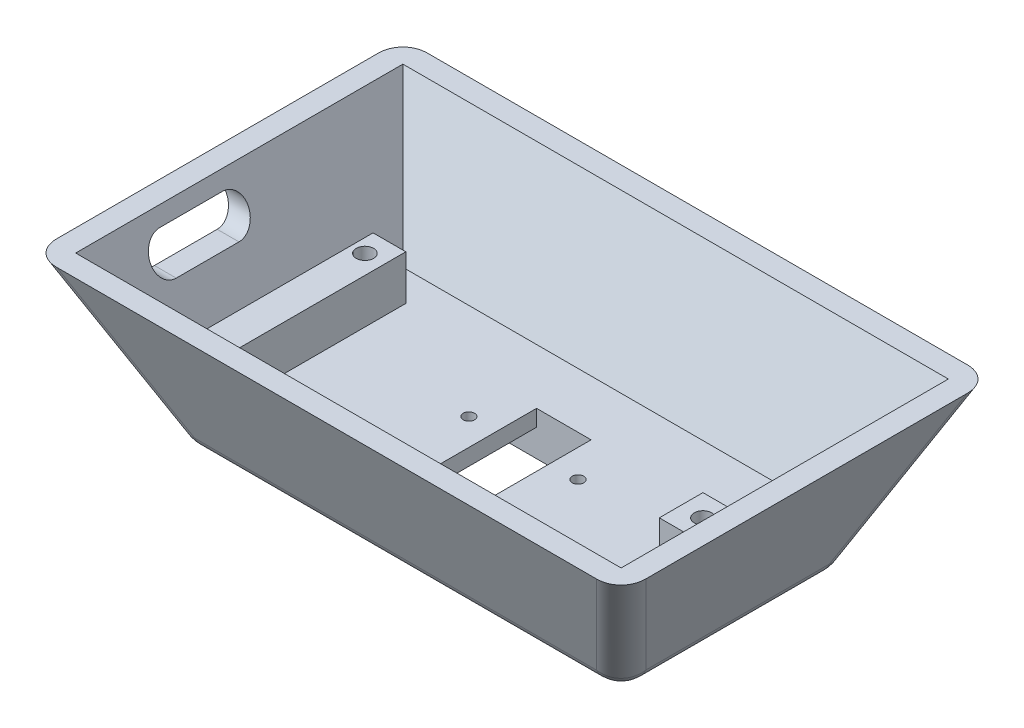
SolidWorks part; units mm, degrees
ref_plane "Front Plane" through (0, 0, 0) normal (0, 0, 1) x (1, 0, 0)
ref_plane "Top Plane" through (0, 0, 0) normal (0, 1, 0) x (1, 0, 0)
ref_plane "Right Plane" through (0, 0, 0) normal (1, 0, 0) x (0, 0, -1)
sketch "Sketch1" plane through (0, 0, 0) normal (0, 1, 0) x (1, 0, 0)
  line L1 (-40, 20) -> (40, 20)
  line L2 (-40, 20) -> (-40, -20)
  line L3 (-40, -20) -> (40, -20)
  line L4 (40, 20) -> (40, -20)
  line L5 (-40, 20) -> (40, -20) construction
  line L6 (-40, -20) -> (40, 20) construction
  point P0 (0, 0)
  dimension "D1" = 40
  dimension "D2" = 80
extrude "Base Extrusion" add sketch "Sketch1" along normal blind 30 draft 25 draft outward yes
sketch "Sketch2" plane through (0, 0, 0) normal (0, -1, 0) x (1, 0, 0)
  line L0 (0, 9.6) -> (0, 20) construction
  line L1 (-15.1, 9.6) -> (15.1, 9.6)
  line L2 (-15.1, 9.6) -> (-15.1, -9.6)
  line L3 (-15.1, -9.6) -> (15.1, -9.6)
  line L4 (15.1, 9.6) -> (15.1, -9.6)
  line L5 (-15.1, 9.6) -> (15.1, -9.6) construction
  line L6 (-15.1, -9.6) -> (15.1, 9.6) construction
  line L7 (-40, 20) -> (40, 20) construction
  point P0 (0, 0)
  dimension "D1" = 19.2
  dimension "D2" = 30.2
  dimension "D3" = 10.4
extrude "Triangle Attach Cutout" cut sketch "Sketch2" against normal blind 5
sketch "Sketch3" plane through (0, 30, 0) normal (0, 1, 0) x (1, 0, 0)
  line L17 (-49.9892, 29.9892) -> (-49.9892, -29.9892)
  line L18 (-49.9892, -29.9892) -> (49.9892, -29.9892)
  line L19 (49.9892, -29.9892) -> (49.9892, 29.9892)
  line L20 (49.9892, 29.9892) -> (-49.9892, 29.9892)
  line L21 (-49.9892, 29.9892) -> (-49.9892, -29.9892)
  line L22 (-49.9892, -29.9892) -> (49.9892, -29.9892)
  line L23 (49.9892, -29.9892) -> (49.9892, 29.9892)
  line L24 (49.9892, 29.9892) -> (-49.9892, 29.9892)
  dimension "D2" = 4
extrude "Shell out the base" cut sketch "Sketch3" against normal blind 22 draft 25
sketch "Sketch5" plane through (0, 5, 0) normal (0, -1, 0) x (1, 0, 0)
  line L0 (0, -2.1) -> (-10, -2.1) construction
  line L1 (0, -1000) -> (0, 49000) construction
  line L2 (-5.1, 5.6) -> (-5.1, 9.6) construction
  line L3 (15.1, 9.6) -> (-15.1, 9.6) construction
  line L4 (-5.1, 9.6) -> (4.9, 9.6) construction
  line L6 (4.9, 9.6) -> (-5.1, 9.6)
  line L7 (4.9, 9.6) -> (4.9, -9.6)
  line L8 (4.9, -9.6) -> (-5.1, -9.6)
  line L9 (-5.1, 9.6) -> (-5.1, -9.6)
  line L11 (-15.1, -9.6) -> (15.1, -9.6) construction
  circle A0 centre (-10, -2.1) radius 1.05
  circle A2 centre (10, -2.1) radius 1.05
  dimension "D3" = 2.1
  dimension "D1" = 10
  dimension "D2" = 2.1
  dimension "D5" = 4
  dimension "D6" = 10
extrude "LED Strip Cutout" cut sketch "Sketch5" against normal up to next
sketch "Sketch13" plane through (0, 0, 0) normal (0, 1, 0) x (1, 0, 0)
  line L0 (-39.7305, -19.7305) -> (39.7305, -19.7305) construction
  line L1 (-39.7305, -19.7305) -> (-33.7305, -19.7305)
  line L2 (-39.7305, -19.7305) -> (-39.7305, 14.2695)
  line L3 (-39.7305, 14.2695) -> (-33.7305, 14.2695)
  line L4 (-33.7305, -19.7305) -> (-33.7305, 14.2695)
  line L5 (31.7305, -4.7305) -> (39.7305, -4.7305)
  line L6 (31.7305, -4.7305) -> (31.7305, 3.2695)
  line L7 (31.7305, 3.2695) -> (39.7305, 3.2695)
  line L8 (39.7305, -4.7305) -> (39.7305, 3.2695)
  line L9 (39.7305, -19.7305) -> (39.7305, 19.7305) construction
  line L10 (31.7305, -0.7305) -> (39.7305, -0.7305) construction
  line L11 (-39.7305, 19.7305) -> (-39.7305, -19.7305) construction
  circle A0 centre (35.7305, -0.7305) radius 1.6002
  circle A1 centre (-37.2305, 10.2695) radius 1.6002
  dimension "D7" = 3.2004
  dimension "D1" = 34
  dimension "D2" = 6
  dimension "D3" = 15
  dimension "D4" = 8
  dimension "D5" = 8
  dimension "D8" = 2.5
  dimension "D9" = 30
extrude "PCB Ledge" add sketch "Sketch13" along normal blind 8.2 from surface starting at face at (-10, 8, -1.05)
sketch "Sketch14" plane through (0, 0, 0) normal (1, 0, 0) x (0, 0, -1)
  line L0 (-15.75, 24.25) -> (-4.25, 24.25) construction
  line L1 (-15.75, 27.5) -> (-4.25, 27.5)
  line L2 (-15.75, 21) -> (-4.25, 21)
  arc A0 (-15.75, 27.5) -> (-15.75, 21) centre (-15.75, 24.25) ccw
  arc A1 (-4.25, 21) -> (-4.25, 27.5) centre (-4.25, 24.25) ccw
  point P2 (-10, 24.25)
  dimension "D1" = 24.25
  dimension "D4" = 11.5
  dimension "D2" = 10
  dimension "D3" = 6.5
extrude "USB-C Cutout" cut sketch "Sketch14" against normal up to next
fillet "Fillet1" radius 5 8 edges at (-40, 0, 0) (0, 0, 20) (40, 0, 0) (0, 0, -20) (-46.9946, 15, 26.9946) (46.9946, 15, 26.9946) (46.9946, 15, -26.9946) (-46.9946, 15, -26.9946)
